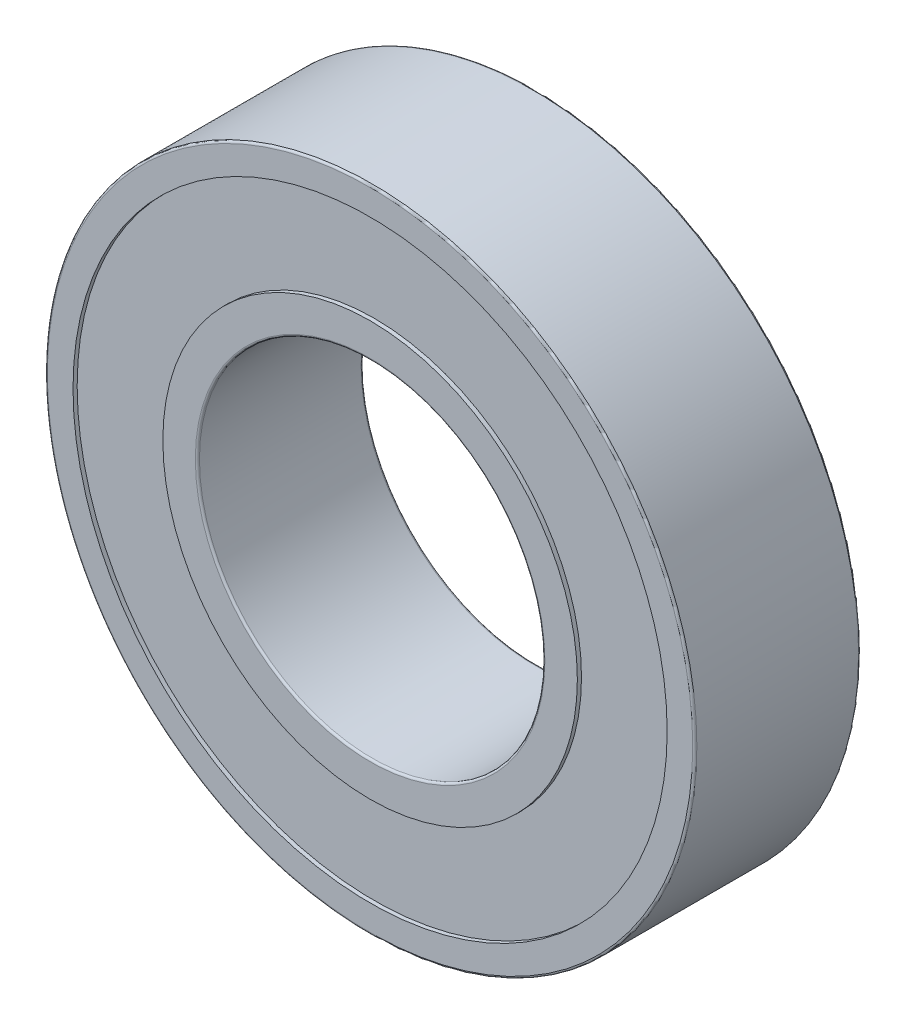
SolidWorks part; units mm, degrees
ref_plane "Front Plane" through (0, 0, 0) normal (0, 0, 1) x (1, 0, 0)
ref_plane "Top Plane" through (0, 0, 0) normal (0, 1, 0) x (1, 0, 0)
ref_plane "Right Plane" through (0, 0, 0) normal (1, 0, 0) x (0, 0, -1)
sketch "Sketch1" plane through (0, 0, 0) normal (0, 0, 1) x (1, 0, 0)
  circle A0 centre (0, 0) radius 12.5
  circle A1 centre (0, 0) radius 23.5
  dimension "D1" = 25
  dimension "D2" = 47
extrude "Boss-Extrude1" add sketch "Sketch1" along normal blind 12
sketch "Sketch2" plane through (0, 0, 12) normal (0, 0, 1) x (1, 0, 0)
  circle A3 centre (0, 0) radius 21.5
  circle A6 centre (0, 0) radius 15
  dimension "D1" = 30
  dimension "D2" = 43
extrude "Cut-Extrude1" cut sketch "Sketch2" against normal blind 0.3
extrude "Cut-Extrude2" cut sketch "Sketch2<2>" along normal blind 0.5 from surface starting at face at (23.5, 0, 0)
sketch "Sketch2<2>" plane through (0, 0, 12) normal (0, 0, 1) x (1, 0, 0) same geometry as "Sketch2"
fillet "Fillet1" radius 0.15 4 edges at (12.5, 0, 12) (23.5, 0, 12) (12.5, 0, 0) (23.5, 0, 0)
